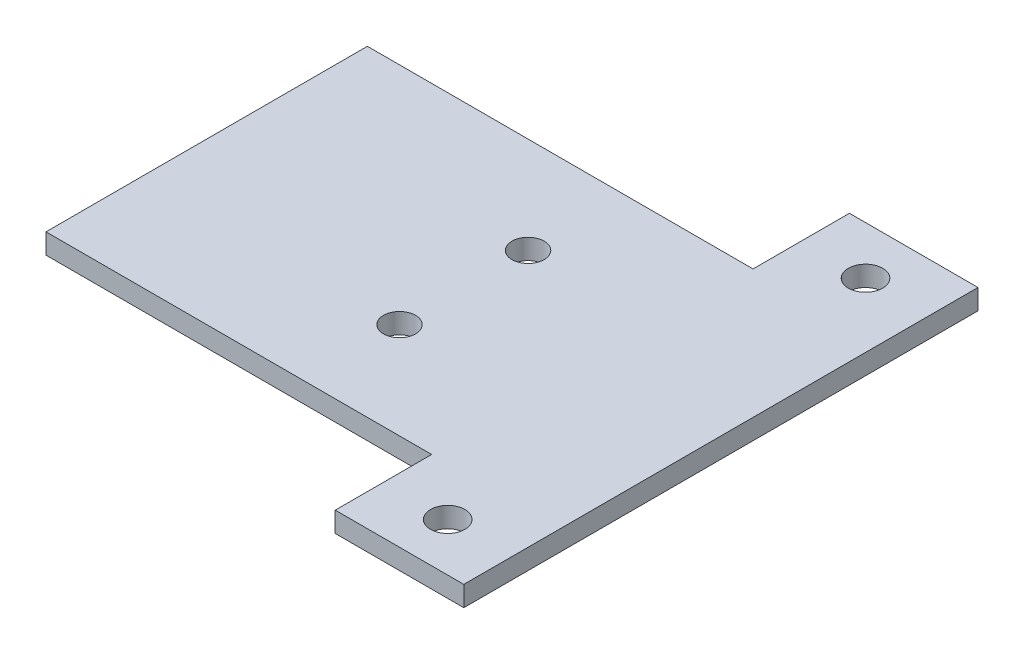
SolidWorks part; units mm, degrees
ref_plane "Front Plane" through (0, 0, 0) normal (0, 0, 1) x (1, 0, 0)
ref_plane "Top Plane" through (0, 0, 0) normal (0, 1, 0) x (1, 0, 0)
ref_plane "Right Plane" through (0, 0, 0) normal (1, 0, 0) x (0, 0, -1)
sketch "Sketch1" plane through (0, 0, 0) normal (0, 1, 0) x (1, 0, 0)
  line L0 (-25.4, 15.875) -> (12.7, 15.875)
  line L1 (12.7, 15.875) -> (12.7, 25.4)
  line L2 (12.7, 25.4) -> (25.4, 25.4)
  line L3 (25.4, 25.4) -> (25.4, -25.4)
  line L4 (25.4, -25.4) -> (12.7, -25.4)
  line L5 (12.7, -25.4) -> (12.7, -15.875)
  line L6 (12.7, -15.875) -> (-25.4, -15.875)
  line L7 (-25.4, -15.875) -> (-25.4, 15.875)
  line L8 (19.05, 20.6375) -> (19.05, -20.6375) construction
  line L9 (0, 6.35) -> (0, -6.35) construction
  circle A0 centre (19.05, 20.6375) radius 1.7
  circle A1 centre (19.05, -20.6375) radius 1.7
  circle A2 centre (0, 6.35) radius 1.5875
  circle A3 centre (0, -6.35) radius 1.5875
  point P18 (0, 0)
  dimension "D5" = 3.4
  dimension "D9" = 3.175
  dimension "D1" = 50.8
  dimension "D2" = 50.8
  dimension "D3" = 12.7
  dimension "D4" = 9.525
  dimension "D6" = 41.275
  dimension "D7" = 6.35
  dimension "D8" = 25.4
  dimension "D10" = 12.7
  dimension "D11" = 9.525
  dimension "D12" = 4.7625
  dimension "D13" = 31.75
extrude "Boss-Extrude1" add sketch "Sketch1" along normal blind 2
